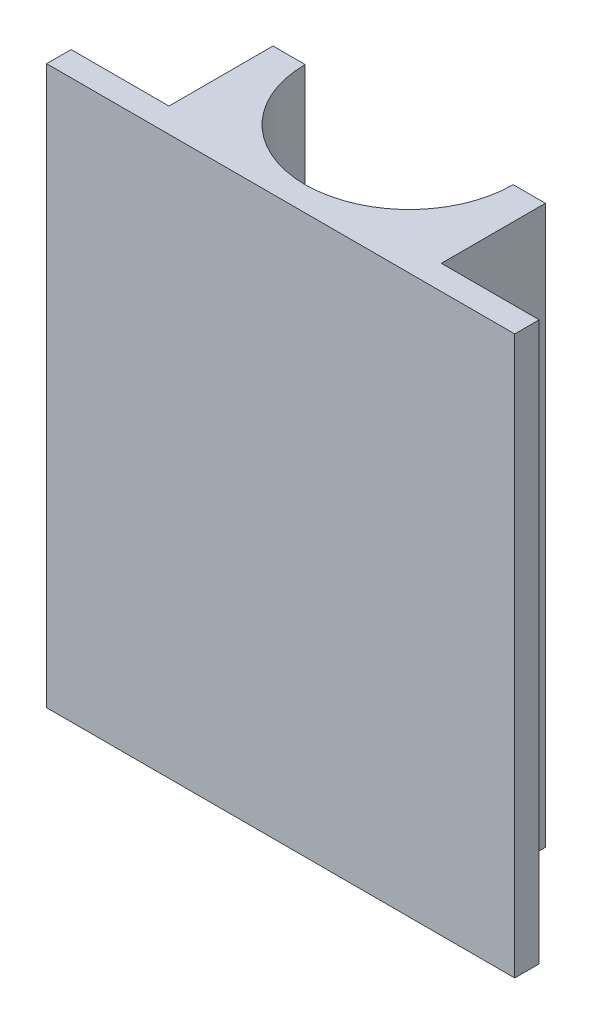
SolidWorks part; units mm, degrees
ref_plane "Front Plane" through (0, 0, 0) normal (0, 0, 1) x (1, 0, 0)
ref_plane "Top Plane" through (0, 0, 0) normal (0, 1, 0) x (1, 0, 0)
ref_plane "Right Plane" through (0, 0, 0) normal (1, 0, 0) x (0, 0, -1)
sketch "Sketch1" plane through (0, 0, 0) normal (0, 1, 0) x (1, 0, 0)
  line L1 (-23.8485, 17.6982) -> (36.9033, 17.6982)
  line L2 (-23.8485, 17.6982) -> (-23.8485, 14.5232)
  line L3 (-23.8485, 14.5232) -> (36.9033, 14.5232)
  line L4 (36.9033, 17.6982) -> (36.9033, 14.5232)
  line L6 (24.2033, 31.1982) -> (-11.1467, 31.1982)
  line L7 (24.2033, 31.1982) -> (24.2033, 17.6982)
  line L8 (24.2033, 17.6982) -> (-11.1467, 17.6982)
  line L9 (-11.1467, 31.1982) -> (-11.1467, 17.6982)
  line L10 (-6.975, 31.1982) -> (-6.675, 31.1982)
  line L11 (20.025, 31.1982) -> (19.725, 31.1982)
  line L12 (6.5283, 38.6577) -> (6.5283, -0.813) construction
  arc A2 (-6.975, 31.1982) -> (20.025, 31.1982) centre (6.525, 31.1982) ccw
  arc A3 (-6.675, 31.1982) -> (19.725, 31.1982) centre (6.525, 31.1982) ccw
  point P13 (0, 0)
  point P17 (0, 0)
  point P18 (0, 0)
  point P19 (0, 0)
  point P20 (0, 0)
  dimension "D1" = 12.7018
  dimension "D2" = 12.7
extrude "Boss-Extrude3" add sketch "Sketch1" along normal blind 72.39 contours A2 L6 L9 L1 | L12 A2 L1 L2 L3 | L1 L12 L3 L4 | A2 L1 L7 L6 region at (-8.6601, 0, -16.1107) region at (-6.9701, 0, -22.9176) region at (20.024, 0, -22.919) region at (21.7158, 0, -16.1107)
extrude "Boss-Extrude4" add sketch "Sketch1<13>" along normal blind 51.39 contours A2 L11 A3 L10
sketch "Sketch1<13>" plane through (0, 0, 0) normal (0, 1, 0) x (1, 0, 0) same geometry as "Sketch1"
